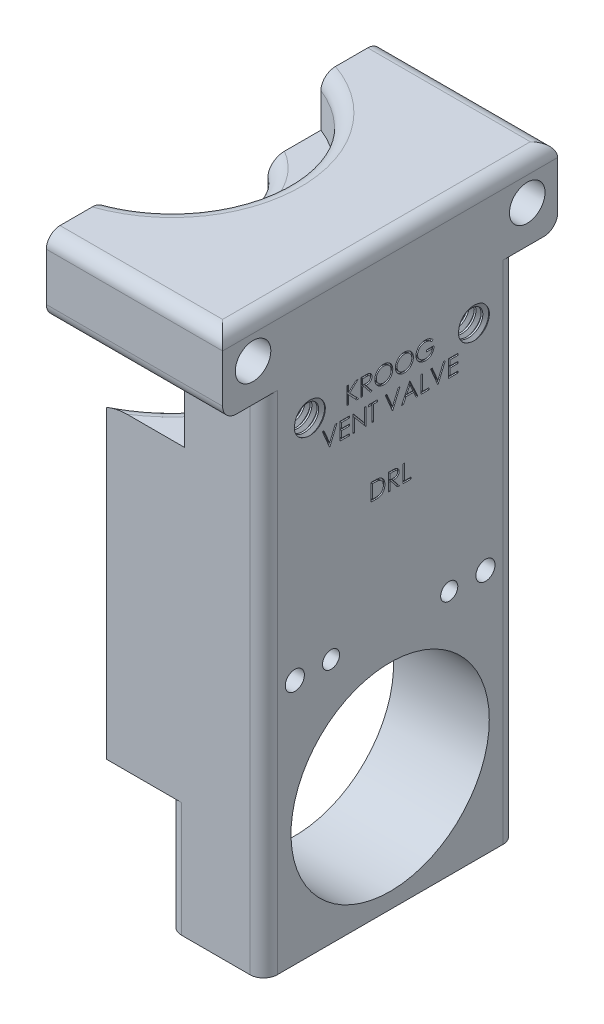
SolidWorks part; units mm, degrees
material "ABS"
ref_plane "Front Plane" through (0, 0, 0) normal (0, 0, 1) x (1, 0, 0)
ref_plane "Top Plane" through (0, 0, 0) normal (0, 1, 0) x (1, 0, 0)
ref_plane "Right Plane" through (0, 0, 0) normal (1, 0, 0) x (0, 0, -1)
sketch "Sketch2" plane through (0, 0, 0) normal (1, 0, 0) x (0, 0, -1)
  line L7 (-23.495, -21.336) -> (23.495, -21.336)
  line L8 (-23.495, -21.336) -> (-23.495, 72.644)
  line L9 (-23.495, 86.614) -> (23.495, 86.614)
  line L10 (23.495, -21.336) -> (23.495, 72.644)
  line L11 (-23.495, 86.614) -> (-31.115, 86.614)
  line L13 (-23.495, 72.644) -> (-31.115, 72.644)
  line L14 (-31.115, 86.614) -> (-31.115, 72.644)
  line L15 (23.495, 86.614) -> (31.115, 86.614)
  line L17 (23.495, 72.644) -> (31.115, 72.644)
  line L18 (31.115, 86.614) -> (31.115, 72.644)
  circle A0 centre (0, 0) radius 18.415
  point P13 (0, -21.336)
  dimension "D1" = 36.83
  dimension "D2" = 21.336
  dimension "D3" = 46.99
  dimension "D4" = 107.95
  dimension "D5" = 13.97
  dimension "D6" = 7.62
extrude "Boss-Extrude1" add sketch "Sketch2" along normal blind 17.78
sketch "Sketch4" plane through (0, 0, 0) normal (-1, 0, 0) x (0, 0, 1)
  line L0 (-23.495, -21.336) -> (-23.495, 72.644) construction
  line L1 (-23.495, 18.796) -> (23.495, 18.796)
  line L2 (-23.495, 18.796) -> (-23.495, 72.644)
  line L4 (23.495, 18.796) -> (23.495, 72.644)
  line L5 (31.115, 86.614) -> (31.115, 72.644) construction
  line L6 (31.115, 72.644) -> (23.495, 72.644) construction
  line L7 (-23.495, 72.644) -> (-31.115, 72.644) construction
  line L8 (-31.115, 72.644) -> (-31.115, 86.614) construction
  line L9 (-31.115, 86.614) -> (31.115, 86.614) construction
  line L10 (31.115, 86.614) -> (31.115, 72.644)
  line L11 (31.115, 72.644) -> (23.495, 72.644)
  line L12 (-23.495, 72.644) -> (-31.115, 72.644)
  line L13 (-31.115, 72.644) -> (-31.115, 86.614)
  line L14 (-31.115, 86.614) -> (31.115, 86.614)
  line L15 (23.495, 72.644) -> (23.495, -21.336) construction
  dimension "D1" = 18.796
extrude "Boss-Extrude2" add sketch "Sketch4" along normal blind 11.43
sketch "Sketch5" plane through (0, 86.614, 0) normal (0, 1, 0) x (1, 0, 0)
  line L0 (0, 0) -> (-22.7305, 0) construction
  line L2 (-11.43, -31.115) -> (-11.43, 31.115) construction
  circle A0 centre (-22.7305, 0) radius 34.925
  circle A1 centre (-22.7305, 0) radius 25.4
  dimension "D2" = 69.85
  dimension "D3" = 50.8
  dimension "D1" = 11.3005
extrude "Cut-Extrude1" cut sketch "Sketch5" against normal blind 15.24 from offset 13.97 contours A1 A0 | A1 region at (-56.6676, 86.614, 0) region at (-22.7305, 86.614, 0) offset against normal yes
extrude "Cut-Extrude2" cut sketch "Sketch5<3>" against normal blind 41.91 from surface contours A1 region at (-22.7305, 86.614, 0) starting at face at (-1.8888, 57.404, 0)
sketch "Sketch5<3>" plane through (0, 86.614, 0) normal (0, 1, 0) x (1, 0, 0) same geometry as "Sketch5"
sketch "Sketch6" plane through (-11.43, 0, 0) normal (-1, 0, 0) x (0, 0, 1)
  line L4 (-31.115, 86.614) -> (-31.115, 72.644)
  line L5 (-31.115, 72.644) -> (31.115, 72.644)
  line L6 (-31.115, 86.614) -> (-31.115, 72.644)
  line L7 (31.115, 72.644) -> (31.115, 86.614)
  line L9 (-31.115, 72.644) -> (31.115, 72.644)
  line L12 (31.115, 72.644) -> (31.115, 86.614)
  line L13 (31.115, 86.614) -> (-31.115, 86.614)
  line L14 (31.115, 86.614) -> (-31.115, 86.614)
  dimension "D1" = 0
extrude "Boss-Extrude3" add sketch "Sketch6" along normal blind 3.5301
sketch "Sketch12" plane through (0, 0, 0) normal (-1, 0, 0) x (0, 0, 1)
  line L0 (-23.495, 18.796) -> (-11.3352, 18.796) construction
  line L1 (-23.495, 18.796) -> (-11.3352, 18.796)
  line L2 (-19.05, 0) -> (-23.495, 0)
  line L3 (-23.495, -21.336) -> (-23.495, 18.796) construction
  line L4 (-23.495, 0) -> (-23.495, 18.796)
  line L5 (19.05, 0) -> (23.495, 0)
  line L6 (11.3352, 18.796) -> (23.495, 18.796)
  line L7 (23.495, 0) -> (23.495, 18.796)
  line L8 (23.495, 18.796) -> (23.495, -21.336) construction
  line L9 (-11.3352, 18.796) -> (-11.3352, 15.3107)
  line L10 (-11.3352, 15.494) -> (-11.3352, 18.796) construction
  line L11 (11.3352, 18.796) -> (11.3352, 15.3107)
  line L12 (11.3352, 18.796) -> (11.3352, 15.494) construction
  arc A0 (-19.05, 0) -> (-11.3352, 15.3107) centre (0, 0) cw
  arc A1 (11.3352, 15.3107) -> (19.05, 0) centre (0, 0) cw
  dimension "D1" = 19.05
extrude "Boss-Extrude5" add sketch "Sketch12" along normal up to surface (11.43 mm away) up to face at (-11.43, 38.1, 23.1214)
sketch "Sketch13" plane through (17.78, 0, 0) normal (1, 0, 0) x (0, 0, -1)
  line L0 (-23.495, -21.336) -> (23.495, -21.336) construction
  line L1 (-23.495, 72.644) -> (-23.495, -21.336) construction
  line L2 (0, 0) -> (0, 86.614) construction
  line L4 (31.115, 86.614) -> (-31.115, 86.614) construction
  circle A0 centre (-17.7038, 24.384) radius 1.778
  circle A1 centre (-10.9728, 24.384) radius 1.5875
  circle A2 centre (17.7038, 24.384) radius 1.778
  circle A3 centre (10.9728, 24.384) radius 1.5875
  dimension "D3" = 3.556
  dimension "D5" = 3.175
  dimension "D1" = 45.72
  dimension "D2" = 5.7912
  dimension "D4" = 6.731
extrude "Cut-Extrude5" cut sketch "Sketch13" against normal through all
sketch "Sketch14" plane through (-11.43, 0, 0) normal (-1, 0, 0) x (0, 0, 1)
  line L0 (10.9728, 24.384) -> (17.7038, 24.384) construction
  line L1 (10.9728, 27.432) -> (17.7038, 27.432)
  line L2 (10.9728, 21.336) -> (17.7038, 21.336)
  line L3 (0, 0) -> (0, 57.404) construction
  line L5 (22.7477, 57.404) -> (-22.7477, 57.404) construction
  line L6 (-10.9728, 24.384) -> (-17.7038, 24.384) construction
  line L7 (-10.9728, 27.432) -> (-17.7038, 27.432)
  line L8 (-10.9728, 21.336) -> (-17.7038, 21.336)
  line L9 (-7.9248, 24.384) -> (-7.9248, 21.336)
  line L10 (-20.7518, 49.784) -> (-7.9248, 49.784)
  line L11 (-20.7518, 49.784) -> (-20.7518, 24.384)
  line L12 (-20.7518, 24.384) -> (-7.9248, 24.384)
  line L13 (-7.9248, 49.784) -> (-7.9248, 24.384)
  line L14 (-20.7518, 49.784) -> (-7.9248, 24.384) construction
  line L15 (-20.7518, 24.384) -> (-7.9248, 49.784) construction
  line L16 (20.7518, 49.784) -> (7.9248, 49.784)
  line L17 (20.7518, 49.784) -> (20.7518, 24.384)
  line L18 (20.7518, 24.384) -> (7.9248, 24.384)
  line L19 (7.9248, 49.784) -> (7.9248, 24.384)
  line L20 (20.7518, 49.784) -> (7.9248, 24.384) construction
  line L21 (20.7518, 24.384) -> (7.9248, 49.784) construction
  line L22 (-10.9728, 21.336) -> (-7.9248, 21.336)
  line L23 (7.9248, 24.384) -> (7.9248, 21.336)
  line L24 (10.9728, 21.336) -> (7.9248, 21.336)
  arc A0 (10.9728, 27.432) -> (10.9728, 21.336) centre (10.9728, 24.384) ccw
  arc A1 (17.7038, 21.336) -> (17.7038, 27.432) centre (17.7038, 24.384) ccw
  arc A2 (-10.9728, 27.432) -> (-10.9728, 21.336) centre (-10.9728, 24.384) cw
  arc A3 (-17.7038, 21.336) -> (-17.7038, 27.432) centre (-17.7038, 24.384) cw
  point P4 (14.3383, 24.384)
  point P17 (-14.3383, 24.384)
  point P22 (-14.3383, 37.084)
  point P27 (14.3383, 37.084)
  line M47 (-11.3352, 18.796) -> (-22.7477, 18.796)
  dimension "D1" = 3.048
  dimension "D2" = 25.4
extrude "Cut-Extrude6" cut sketch "Sketch14" against normal blind 13.97 contours A3 L8 A2 L12 M47 | L9 A2 L22 | L11 A3 L7 A2 L13 L10 | A3 L12 A2 L7 | L2 A1 L18 A0 | A0 L23 L24 | L18 A1 L1 A0 | A1 L17 L16 L19 A0 L1 region at (-11.43, 38.4454, 14.3383) region at (-11.43, 25.8122, 14.3383) region at (-11.43, 22.0168, 8.6056) region at (-11.43, 22.9558, 14.3383) region at (-11.43, 25.8122, -14.3383) region at (-11.43, 38.4454, -14.3383) region at (-11.43, 22.9558, -14.3383) region at (-11.43, 22.0168, -8.6056)
sketch "Sketch15" plane through (-14.9601, 0, 0) normal (-1, 0, 0) x (0, 0, 1)
  line L0 (-31.115, 79.629) -> (-19.812, 79.629) construction
  line L1 (-31.115, 86.614) -> (-31.115, 72.644) construction
  line L3 (0, 72.644) -> (0, 86.614) construction
  line L4 (-31.115, 72.644) -> (31.115, 72.644) construction
  line L5 (31.115, 86.614) -> (-31.115, 86.614) construction
  line L6 (0, 0) -> (0, 86.614) construction
  circle A0 centre (-25.4635, 79.629) radius 3.302
  circle A1 centre (25.4635, 79.629) radius 3.302
  dimension "D1" = 6.604
  dimension "D2" = 19.812
extrude "Cut-Extrude7" cut sketch "Sketch15" against normal through all
sketch "Sketch17" plane through (0, 86.614, 0) normal (0, 1, 0) x (1, 0, 0)
  line L0 (-14.9601, -31.115) -> (-14.9601, 31.115) construction
  circle A0 centre (-22.7071, 0) radius 21.336
  dimension "D2" = 42.672
  dimension "D1" = 7.747
extrude "Cut-Extrude9" cut sketch "Sketch17" against normal blind 8.89
sketch "Sketch18" plane through (0, 77.724, 0) normal (0, 1, 0) x (1, 0, 0)
  line L0 (-22.7071, 0) -> (0, 0) construction
  arc A0 (-14.9601, -19.8799) -> (-14.9601, 19.8799) centre (-22.7071, 0) ccw construction
  arc A1 (-14.9601, -19.8799) -> (-14.9601, 19.8799) centre (-22.7071, 0) ccw construction
  circle A2 centre (-22.7071, 0) radius 12.7
  circle A3 centre (-5.2299, 0) radius 2.0509
  dimension "D1" = 25.4
  dimension "D2" = 4.1017
  dimension "D3" = 17.4772
extrude "Cut-Extrude10" cut sketch "Sketch18" against normal blind 8.89
sketch "Sketch16" plane through (17.78, 0, 0) normal (1, 0, 0) x (0, 0, -1)
  line L0 (-23.495, 63.754) -> (23.495, 63.754) construction
  line L1 (-23.495, 58.674) -> (23.495, 58.674) construction
  line L2 (23.495, -21.336) -> (23.495, 72.644) construction
  line L3 (-23.495, 72.644) -> (-23.495, -21.336) construction
  line L4 (-23.495, 45.974) -> (23.495, 45.974) construction
  line L5 (31.115, 86.614) -> (-31.115, 86.614) construction
  text T0 "KROOG\r\n"
  text T1 "VENT VALVE"
  text T2 "DRL"
  dimension "D1" = 22.86
  dimension "D2" = 12.7
  dimension "D3" = 5.08
extrude "Cut-Extrude8" cut sketch "Sketch16" against normal blind 0.254
fillet "Fillet1" radius 2.54 2 edges at (-1.3711, 86.614, 0) (-10.0071, 77.724, 0)
fillet "Fillet6" radius 1.27 4 edges at (2.54, 24.384, -15.9258) (2.54, 24.384, -9.3853) (2.54, 24.384, 19.4818) (2.54, 24.384, 12.5603)
fillet "Fillet7" radius 2.54 10 edges at (2.6695, 57.404, 0) (0, -10.668, -23.495) (0, -10.668, 23.495) (17.78, 25.654, -23.495) (17.78, 25.654, 23.495) (17.78, 86.614, 0) (1.41, 72.644, 31.115) (1.41, 86.614, 31.115) (1.41, 72.644, -31.115) (1.41, 86.614, -31.115)
sketch "Sketch19" plane through (0, 72.644, 0) normal (0, -1, 0) x (1, 0, 0)
  circle A0 centre (-5.2299, 0) radius 4.064
  dimension "D1" = 8.128
extrude "Cut-Extrude11" cut sketch "Sketch19" against normal blind 1.27
sketch "Sketch20" plane through (17.78, 0, 0) normal (1, 0, 0) x (0, 0, -1)
  line L0 (-28.575, 86.614) -> (28.575, 86.614) construction
  line L1 (0, 86.614) -> (0, 0) construction
  circle A0 centre (-15.24, 65.024) radius 1.905
  circle A1 centre (15.24, 65.024) radius 1.905
  point P0 (-15.24, 65.024)
  point P4 (0, 86.614)
  point P13 (15.24, 65.024)
  dimension "D2" = 3.81
  dimension "D1" = 21.59
  dimension "D3" = 15.24
hole_wizard "Tap Drill for 1/4-20 Tap1" positions "Sketch20" profile "Sketch21" hole size "1/4-20" standard "ANSI Inch"
sketch "Sketch21" plane through (17.78, 65.024, 15.24) normal (0, 1, 0) x (0, 0, -1)
  line L0 (0, 0) -> (0, 20.5838)
  line L1 (0, 20.5838) -> (2.5527, 19.05)
  line L2 (2.5527, 19.05) -> (2.5527, 0)
  line L5 (2.5527, 0) -> (0, 0)
  line L10 (0, 20.5838) -> (-2.5527, 19.05) construction
  line L11 (0, -6.35) -> (0, 107.95) construction
  dimension "Hole Dia." = 5.1054
  dimension "Hole Depth" = 19.05
  dimension "Drill Angle" = 118
thread "Thread1" pitch 1.27 method cut profile "Thread Profile1" start angle 0, offset 1, length 12.7, pitch 1.27, diameter 5.1054
ref_plane "Plane1" through (18.78, 65.024, 17.7927) normal (0, -1, 0) x (0, 0, 1)
sketch "Thread Profile1" plane through (18.78, 65.024, 17.7927) normal (0, -1, 0) x (0, 0, 1)
  line L0 (0, 0) -> (0, 1.27) construction
  line L1 (0, 0) -> (0.6874, 0.3969)
  line L2 (0.6874, 0.3969) -> (0.6874, 0.5556)
  line L3 (0.6874, 0.5556) -> (0, 0.9525)
  line L4 (0.6874, 0.4762) -> (0, 0.4762) construction
  line L11 (0, 0) -> (0, 0.9525)
  point P2 (0, 0)
  dimension "Pitch" = 1.27
  dimension "Profile_Angle" = 60
  dimension "Profile_Land" = 0.1588
  dimension "Profile_Height" = 0.6874
thread "Thread2" pitch 1.27 method cut profile "Thread Profile2" start angle 0, offset 1, length 12.7, pitch 1.27, diameter 5.1054
ref_plane "Plane2" through (18.78, 65.024, -12.6873) normal (0, -1, 0) x (0, 0, 1)
sketch "Thread Profile2" plane through (18.78, 65.024, -12.6873) normal (0, -1, 0) x (0, 0, 1)
  line L0 (0, 0) -> (0, 1.27) construction
  line L1 (0, 0) -> (0.6874, 0.3969)
  line L2 (0.6874, 0.3969) -> (0.6874, 0.5556)
  line L3 (0.6874, 0.5556) -> (0, 0.9525)
  line L4 (0.6874, 0.4762) -> (0, 0.4762) construction
  line L11 (0, 0) -> (0, 0.9525)
  point P2 (0, 0)
  dimension "Pitch" = 1.27
  dimension "Profile_Angle" = 60
  dimension "Profile_Land" = 0.1588
  dimension "Profile_Height" = 0.6874
